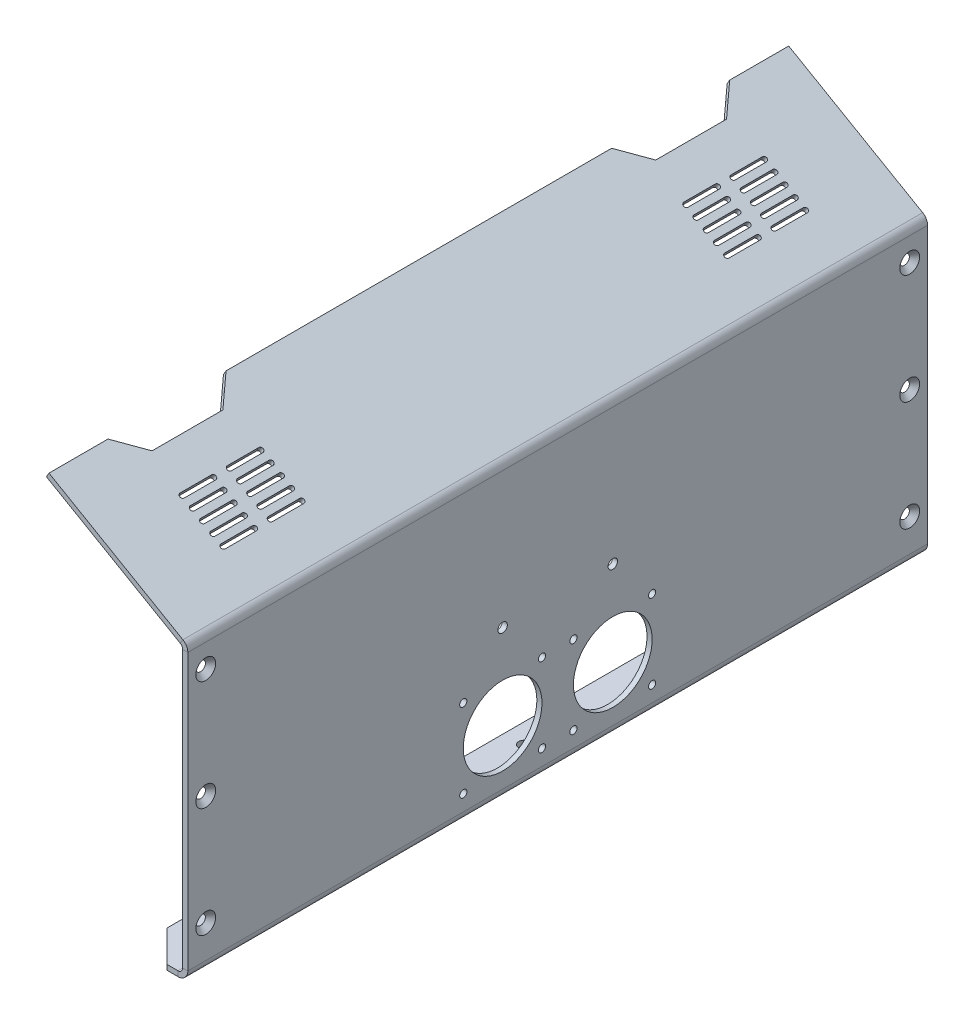
SolidWorks part; units mm, degrees
note: The reader was unsure of these and kept them because the rebuilt part matched: bend radius of "BaseBend1", "BaseBend2".
material "5052-H32"
ref_plane "Front Plane" through (0, 0, 0) normal (0, 0, 1) x (1, 0, 0)
ref_plane "Top Plane" through (0, 0, 0) normal (0, 1, 0) x (1, 0, 0)
ref_plane "Right Plane" through (0, 0, 0) normal (1, 0, 0) x (0, 0, -1)
sketch "Sketch1" plane through (0, 0, 0) normal (0, 0, 1) x (1, 0, 0)
  line L0 (-30, 0) -> (0, 0)
  line L1 (0, 0) -> (0, 180)
  line L2 (0, 180) -> (-86.6025, 230)
  dimension "D1" = 30
  dimension "D2" = 180
  dimension "D3" = 120
  dimension "D4" = 100
base flange "Base-Flange1" sketch "Sketch1" end condition mid plane depth 470 reverse direction no thickness 3.26 reverse thickness direction no bend radius 3
bend "BaseBend1" bend radius 3 bend angle 90 parameters "D5"=1
bend "BaseBend2" bend radius 3 bend angle 60 parameters "D5"=3
sketch "Sketch6" plane through (0, 0, 0) normal (0, 1, 0) x (1, 0, 0)
  line L1 (-17.387, -0.5952) -> (-17.387, -200.5952) construction
  line L2 (-17.387, -0.5952) -> (-17.387, 199.4048) construction
  circle A0 centre (-17.387, -0.5952) radius 3.5
  circle A1 centre (-17.387, -200.5952) radius 3.5
  circle A2 centre (-17.387, -100.5952) radius 3.5
  circle A3 centre (-17.387, 199.4048) radius 3.5
  circle A4 centre (-17.387, 99.4048) radius 3.5
  dimension "D2" = 7
  dimension "D1" = 200
extrude "Cut-Extrude1" cut sketch "Sketch6" against normal blind 10 normal cut yes
sketch "Sketch7" plane through (0, 0, 0) normal (0, 1, 0) x (1, 0, 0)
  line L0 (0, 0) -> (-64.8841, 0) construction
  line L1 (-30, -115.5952) -> (-3, -142.5952)
  line L2 (-30, -235) -> (-30, 235) construction
  line L3 (-3, -142.5952) -> (-3, -158.5952)
  line L4 (-3, -158.5952) -> (-30, -185.5952)
  line L5 (-3, -235) -> (-3, 235) construction
  line L6 (-30, -115.5952) -> (-30, -185.5952)
  line L7 (-30, 115.5952) -> (-30, 185.5952)
  line L8 (-3, 158.5952) -> (-30, 185.5952)
  line L9 (-3, 142.5952) -> (-3, 158.5952)
  line L10 (-30, 115.5952) -> (-3, 142.5952)
  circle A0 centre (-17.387, -100.5952) radius 3.5 construction
  circle A1 centre (-17.387, -200.5952) radius 3.5 construction
  dimension "D1" = 15
  dimension "D2" = 15
extrude "Cut-Extrude2" [suppressed] cut sketch "Sketch7" against normal up to surface (3.175 mm away)
chamfer "Chamfer1" distance 20 angle 45 2 edges at (-30, -1.63, 235) (-30, -1.63, -235)
sketch "Sketch8" plane through (3.26, 0, 0) normal (1, 0, 0) x (0, 0, -1)
  line L0 (0, 0) -> (0, 178.2679) construction
  line L1 (-235, 178.2679) -> (235, 178.2679) construction
  circle A0 centre (-223.6192, 163.426) radius 3
  circle A1 centre (-223.6192, 93.576) radius 3
  circle A2 centre (-223.6192, 23.726) radius 3
  circle A3 centre (223.6192, 23.726) radius 3
  circle A4 centre (223.6192, 93.576) radius 3
  circle A5 centre (223.6192, 163.426) radius 3
  dimension "D1" = 6
extrude "Cut-Extrude3" cut sketch "Sketch8" against normal up to surface (3.26 mm away) normal cut yes up to face at (0, 90.634, 0)
sketch "Sketch9" [suppressed] plane through (0, -3.175, 0) normal (0, -1, 0) x (-1, 0, 0)
  line L0 (3.048, -163.048) -> (25, -185) construction
  line L1 (14.024, -174.024) -> (-3.175, -174.024)
  line L2 (14.024, -174.024) -> (14.024, -125.976)
  line L3 (14.024, -125.976) -> (-3.175, -125.976)
  line L4 (-3.175, -174.024) -> (-3.175, -125.976)
  line L5 (25, -115) -> (3.048, -136.952) construction
  line L6 (-3.175, -235) -> (-3.175, 235) construction
  line L7 (0, 0) -> (25, 0) construction
  line L8 (25, -115) -> (25, 115) construction
  line L9 (-3.175, 174.024) -> (-3.175, 125.976)
  line L10 (14.024, 125.976) -> (-3.175, 125.976)
  line L11 (14.024, 174.024) -> (14.024, 125.976)
  line L12 (14.024, 174.024) -> (-3.175, 174.024)
extrude "Cut-Extrude4" [suppressed] cut sketch "Sketch9" against normal blind 15
sketch "Sketch10" plane through (79.5723, 137.8232, 0) normal (0.5, 0.866, 0) x (0.866, -0.5, 0)
  line L1 (-163.366, 177.5) -> (-118.366, 177.5)
  line L2 (-163.366, 177.5) -> (-163.366, 92.5)
  line L3 (-163.366, 92.5) -> (-118.366, 92.5)
  line L4 (-118.366, 177.5) -> (-118.366, 92.5)
  line L5 (-163.366, 177.5) -> (-118.366, 92.5) construction
  line L6 (-163.366, 92.5) -> (-118.366, 177.5) construction
  line L7 (-91.7321, 235) -> (-190, 235) construction
  point P0 (-140.866, 135)
  point P10 (-140.866, 235)
  dimension "D1" = 45
  dimension "D2" = 85
  dimension "D3" = 100
sketch "Sketch11" plane through (3.26, 0, 0) normal (1, 0, 0) x (0, 0, -1)
  line L0 (0, 3) -> (0, 178.2679) construction
  line L1 (-235, 3) -> (235, 3) construction
  line L2 (-235, 178.2679) -> (235, 178.2679) construction
  line L3 (-10, 63) -> (-60, 63) construction
  line L4 (-10, 63) -> (-10, 13) construction
  line L5 (-10, 13) -> (-60, 13) construction
  line L6 (-60, 63) -> (-60, 13) construction
  line L7 (-10, 63) -> (-60, 13) construction
  line L8 (-10, 13) -> (-60, 63) construction
  line L9 (10, 13) -> (60, 63) construction
  line L10 (10, 63) -> (60, 13) construction
  line L11 (60, 63) -> (60, 13) construction
  line L12 (10, 13) -> (60, 13) construction
  line L13 (10, 63) -> (10, 13) construction
  line L14 (10, 63) -> (60, 63) construction
  circle A0 centre (-60, 63) radius 2.286
  circle A1 centre (-10, 63) radius 2.286
  circle A2 centre (-10, 13) radius 2.286
  circle A3 centre (-60, 13) radius 2.286
  circle A4 centre (-35, 38) radius 25
  circle A5 centre (35, 38) radius 25
  circle A6 centre (60, 13) radius 2.286
  circle A7 centre (10, 13) radius 2.286
  circle A8 centre (10, 63) radius 2.286
  circle A9 centre (60, 63) radius 2.286
  point P6 (-35, 38)
  dimension "D3" = 4.572
  dimension "D1" = 35
  dimension "D2" = 35
  dimension "D4" = 50
extrude "Cut-Extrude5" cut sketch "Sketch11" against normal up to surface (3.26 mm away) normal cut yes up to face at (0, 163.426, -220.6192)
sketch "Sketch12" plane through (79.5723, 137.8232, 0) normal (0.5, 0.866, 0) x (0.866, -0.5, 0)
  line L0 (-91.7321, -235) -> (-190, -235) construction
  line L2 (-190, -235) -> (-190, 235) construction
  circle A0 centre (-130, -155) radius 10
  circle A1 centre (-130, -115) radius 10
  dimension "D1" = 20
  dimension "D2" = 80
  dimension "D3" = 40
  dimension "D4" = 60
sketch "Sketch14" plane through (0, 0, 0) normal (-1, 0, 0) x (0, 0, 1)
  circle A0 centre (35, 91.949) radius 3
  circle A1 centre (-35, 91.949) radius 3
  dimension "D1" = 6
extrude "Cut-Extrude7" cut sketch "Sketch14" against normal blind 10 normal cut yes
sketch "Sketch15" plane through (79.5723, 137.8232, 0) normal (0.5, 0.866, 0) x (0.866, -0.5, 0)
  line L0 (-150, -165) -> (-150, -185) construction
  line L1 (-148.5, -165) -> (-148.5, -185)
  line L2 (-151.5, -165) -> (-151.5, -185)
  line L3 (-91.7321, -235) -> (-190, -235) construction
  line L4 (-190, -235) -> (-190, 235) construction
  line L5 (-142.5, -165) -> (-142.5, -185) construction
  line L6 (-141, -165) -> (-141, -185)
  line L7 (-144, -165) -> (-144, -185)
  line L8 (-135, -165) -> (-135, -185) construction
  line L9 (-133.5, -165) -> (-133.5, -185)
  line L10 (-136.5, -165) -> (-136.5, -185)
  line L11 (-127.5, -165) -> (-127.5, -185) construction
  line L12 (-126, -165) -> (-126, -185)
  line L13 (-129, -165) -> (-129, -185)
  line L14 (-120, -165) -> (-120, -185) construction
  line L15 (-118.5, -165) -> (-118.5, -185)
  line L16 (-121.5, -165) -> (-121.5, -185)
  line L17 (-142.5, -135) -> (-142.5, -155) construction
  line L18 (-141, -135) -> (-141, -155)
  line L19 (-144, -135) -> (-144, -155)
  line L20 (-135, -135) -> (-135, -155) construction
  line L21 (-133.5, -135) -> (-133.5, -155)
  line L22 (-136.5, -135) -> (-136.5, -155)
  line L23 (-127.5, -135) -> (-127.5, -155) construction
  line L24 (-126, -135) -> (-126, -155)
  line L25 (-129, -135) -> (-129, -155)
  line L26 (-120, -135) -> (-120, -155) construction
  line L27 (-118.5, -135) -> (-118.5, -155)
  line L28 (-121.5, -135) -> (-121.5, -155)
  line L29 (-150, -135) -> (-150, -155) construction
  line L30 (-148.5, -135) -> (-148.5, -155)
  line L31 (-151.5, -135) -> (-151.5, -155)
  line L32 (-150, -165) -> (-142.5, -165) construction
  line L33 (-150, -165) -> (-150, -135) construction
  line L34 (-190, 0) -> (-91.7321, 0) construction
  line L35 (-91.7321, -235) -> (-91.7321, 235) construction
  line L36 (-150, 165) -> (-150, 185) construction
  line L37 (-148.5, 165) -> (-148.5, 185)
  line L38 (-151.5, 165) -> (-151.5, 185)
  line L39 (-142.5, 165) -> (-142.5, 185) construction
  line L40 (-141, 165) -> (-141, 185)
  line L41 (-144, 165) -> (-144, 185)
  line L42 (-135, 165) -> (-135, 185) construction
  line L43 (-133.5, 165) -> (-133.5, 185)
  line L44 (-136.5, 165) -> (-136.5, 185)
  line L45 (-127.5, 165) -> (-127.5, 185) construction
  line L46 (-126, 165) -> (-126, 185)
  line L47 (-129, 165) -> (-129, 185)
  line L48 (-120, 165) -> (-120, 185) construction
  line L49 (-118.5, 165) -> (-118.5, 185)
  line L50 (-121.5, 165) -> (-121.5, 185)
  line L51 (-142.5, 135) -> (-142.5, 155) construction
  line L52 (-141, 135) -> (-141, 155)
  line L53 (-144, 135) -> (-144, 155)
  line L54 (-135, 135) -> (-135, 155) construction
  line L55 (-133.5, 135) -> (-133.5, 155)
  line L56 (-136.5, 135) -> (-136.5, 155)
  line L57 (-127.5, 135) -> (-127.5, 155) construction
  line L58 (-126, 135) -> (-126, 155)
  line L59 (-129, 135) -> (-129, 155)
  line L60 (-120, 135) -> (-120, 155) construction
  line L61 (-118.5, 135) -> (-118.5, 155)
  line L62 (-121.5, 135) -> (-121.5, 155)
  line L63 (-150, 135) -> (-150, 155) construction
  line L64 (-148.5, 135) -> (-148.5, 155)
  line L65 (-151.5, 135) -> (-151.5, 155)
  line L66 (-150, 165) -> (-150, 135) construction
  line L67 (-150, 165) -> (-142.5, 165) construction
  arc A0 (-148.5, -165) -> (-151.5, -165) centre (-150, -165) ccw
  arc A1 (-151.5, -185) -> (-148.5, -185) centre (-150, -185) ccw
  arc A2 (-141, -165) -> (-144, -165) centre (-142.5, -165) ccw
  arc A3 (-144, -185) -> (-141, -185) centre (-142.5, -185) ccw
  arc A4 (-133.5, -165) -> (-136.5, -165) centre (-135, -165) ccw
  arc A5 (-136.5, -185) -> (-133.5, -185) centre (-135, -185) ccw
  arc A6 (-126, -165) -> (-129, -165) centre (-127.5, -165) ccw
  arc A7 (-129, -185) -> (-126, -185) centre (-127.5, -185) ccw
  arc A8 (-118.5, -165) -> (-121.5, -165) centre (-120, -165) ccw
  arc A9 (-121.5, -185) -> (-118.5, -185) centre (-120, -185) ccw
  arc A10 (-141, -135) -> (-144, -135) centre (-142.5, -135) ccw
  arc A11 (-144, -155) -> (-141, -155) centre (-142.5, -155) ccw
  arc A12 (-133.5, -135) -> (-136.5, -135) centre (-135, -135) ccw
  arc A13 (-136.5, -155) -> (-133.5, -155) centre (-135, -155) ccw
  arc A14 (-126, -135) -> (-129, -135) centre (-127.5, -135) ccw
  arc A15 (-129, -155) -> (-126, -155) centre (-127.5, -155) ccw
  arc A16 (-118.5, -135) -> (-121.5, -135) centre (-120, -135) ccw
  arc A17 (-121.5, -155) -> (-118.5, -155) centre (-120, -155) ccw
  arc A18 (-148.5, -135) -> (-151.5, -135) centre (-150, -135) ccw
  arc A19 (-151.5, -155) -> (-148.5, -155) centre (-150, -155) ccw
  arc A20 (-148.5, 165) -> (-151.5, 165) centre (-150, 165) cw
  arc A21 (-151.5, 185) -> (-148.5, 185) centre (-150, 185) cw
  arc A22 (-141, 165) -> (-144, 165) centre (-142.5, 165) cw
  arc A23 (-144, 185) -> (-141, 185) centre (-142.5, 185) cw
  arc A24 (-133.5, 165) -> (-136.5, 165) centre (-135, 165) cw
  arc A25 (-136.5, 185) -> (-133.5, 185) centre (-135, 185) cw
  arc A26 (-126, 165) -> (-129, 165) centre (-127.5, 165) cw
  arc A27 (-129, 185) -> (-126, 185) centre (-127.5, 185) cw
  arc A28 (-118.5, 165) -> (-121.5, 165) centre (-120, 165) cw
  arc A29 (-121.5, 185) -> (-118.5, 185) centre (-120, 185) cw
  arc A30 (-141, 135) -> (-144, 135) centre (-142.5, 135) cw
  arc A31 (-144, 155) -> (-141, 155) centre (-142.5, 155) cw
  arc A32 (-133.5, 135) -> (-136.5, 135) centre (-135, 135) cw
  arc A33 (-136.5, 155) -> (-133.5, 155) centre (-135, 155) cw
  arc A34 (-126, 135) -> (-129, 135) centre (-127.5, 135) cw
  arc A35 (-129, 155) -> (-126, 155) centre (-127.5, 155) cw
  arc A36 (-118.5, 135) -> (-121.5, 135) centre (-120, 135) cw
  arc A37 (-121.5, 155) -> (-118.5, 155) centre (-120, 155) cw
  arc A38 (-148.5, 135) -> (-151.5, 135) centre (-150, 135) cw
  arc A39 (-151.5, 155) -> (-148.5, 155) centre (-150, 155) cw
  point P2 (-150, -175)
  point P15 (-142.5, -175)
  point P22 (-135, -175)
  point P29 (-127.5, -175)
  point P36 (-120, -175)
  point P43 (-142.5, -145)
  point P50 (-135, -145)
  point P57 (-127.5, -145)
  point P64 (-120, -145)
  point P71 (-150, -145)
  point P83 (-150, 175)
  point P90 (-142.5, 175)
  point P97 (-135, 175)
  point P104 (-127.5, 175)
  point P111 (-120, 175)
  point P118 (-142.5, 145)
  point P125 (-135, 145)
  point P132 (-127.5, 145)
  point P139 (-120, 145)
  point P146 (-150, 145)
  dimension "D2" = 1.5
  dimension "D1" = 60
  dimension "D3" = 40
  dimension "D4" = 20
  dimension "D7" = 7.5
  dimension "D8" = 30
  dimension "D5" = 5
  dimension "D6" = 2
extrude "Cut-Extrude8" cut sketch "Sketch15" against normal blind 10
sketch "Sketch16" plane through (79.5723, 137.8232, 0) normal (0.5, 0.866, 0) x (0.866, -0.5, 0)
  line L0 (-190, -235) -> (-190, 235) construction
  line L1 (-175, -130) -> (-190, -130)
  line L2 (-175, -130) -> (-175, -190)
  line L3 (-175, -190) -> (-190, -190)
  line L4 (-190, -130) -> (-190, -190)
  line L5 (-175, -130) -> (-190, -190) construction
  line L6 (-175, -190) -> (-190, -130) construction
  line L8 (-142.5, -156.5) -> (-142.5, -163.5) construction
  line L9 (-91.7321, 0) -> (-190, 0) construction
  line L10 (-91.7321, -235) -> (-91.7321, 235) construction
  line L11 (-142.5, 156.5) -> (-142.5, 163.5) construction
  line L12 (-175, 190) -> (-190, 130) construction
  line L13 (-175, 130) -> (-190, 190) construction
  line L14 (-190, 130) -> (-190, 190)
  line L15 (-175, 190) -> (-190, 190)
  line L16 (-175, 130) -> (-175, 190)
  line L17 (-175, 130) -> (-190, 130)
  arc A0 (-144, -155) -> (-141, -155) centre (-142.5, -155) ccw construction
  arc A1 (-141, -165) -> (-144, -165) centre (-142.5, -165) ccw construction
  point P0 (-182.5, -160)
  point P16 (-142.5, -160)
  point P27 (-142.5, 160)
  point P28 (-182.5, 160)
  dimension "D1" = 15
  dimension "D2" = 60
extrude "Cut-Extrude9" cut sketch "Sketch16" against normal blind 10 normal cut yes
chamfer "Chamfer2" distance 7.5 angle 45 8 edges at (-85.7875, 231.4116, -190) (-72.7972, 223.9116, -190) (-72.7972, 223.9116, -130) (-85.7875, 231.4116, -130) (-85.7875, 231.4116, 130) (-72.7972, 223.9116, 130) (-72.7972, 223.9116, 190) (-85.7875, 231.4116, 190)
chamfer "Chamfer3" distance 3.3 angle 45 6 edges at (3.26, 163.426, 220.6192) (3.26, 163.426, -220.6192) (3.26, 93.576, -220.6192) (3.26, 23.726, -220.6192) (3.26, 23.726, 220.6192) (3.26, 93.576, 220.6192)
sketch "Bend-Lines1" [suppressed] plane through (0, 0, 0) normal (0, 1, 0) x (1, 0, 0)
sketch "Bounding-Box1" [suppressed] plane through (0, 0, 0) normal (0, 1, 0) x (1, 0, 0)
sheet metal parameters "Sheet-Metal1" thickness 3.26 parameters "D1"=2.54
flat pattern "Flat-Pattern1" [suppressed]
sketch "Bend-Lines2" plane through (0, 0, 0) normal (-1, 0, 0) x (0, 0, 1)
  line L0 (235, -0.2) -> (-235, -0.2) construction
  line L1 (235, -0.2) -> (-235, -0.2) construction
sketch3d "Bounding-Box2" [suppressed]
  line L0 (-470, -25.4, 0) -> (0, -25.4, 0) construction
  line L1 (-470, 120, 0) -> (0, 120, 0) construction
  line L2 (-470, -25.4, 0) -> (-470, 120, 0) construction
  line L3 (0, -25.4, 0) -> (0, 120, 0) construction
bend of the flat pattern "Flatten-<BaseBend1>1"
bend of the flat pattern "Flatten-<BaseBend2>1"
sheet metal parameters "Sheet-Metal2" thickness 3.26 parameters "D1"=2.54
flat pattern "Flat-Pattern1" [suppressed]
sketch "Bend-Lines2" plane through (0, 0, 0) normal (-1, 0, 0) x (0, 0, 1)
  line L0 (235, -0.2) -> (-235, -0.2) construction
  line L1 (235, -0.2) -> (-235, -0.2) construction
sketch3d "Bounding-Box2" [suppressed]
  line L0 (-470, -25.4, 0) -> (0, -25.4, 0) construction
  line L1 (-470, 120, 0) -> (0, 120, 0) construction
  line L2 (-470, -25.4, 0) -> (-470, 120, 0) construction
  line L3 (0, -25.4, 0) -> (0, 120, 0) construction
bend of the flat pattern "Flatten-<BaseBend1>1"
bend of the flat pattern "Flatten-<BaseBend2>2"
sheet metal parameters "Sheet-Metal3" thickness 3.26 parameters "D1"=2.54
flat pattern "Flat-Pattern1" [suppressed]
sketch "Bend-Lines2" plane through (0, 0, 0) normal (-1, 0, 0) x (0, 0, 1)
  line L0 (235, -0.2) -> (-235, -0.2) construction
  line L1 (235, -0.2) -> (-235, -0.2) construction
sketch3d "Bounding-Box2" [suppressed]
  line L0 (-470, -25.4, 0) -> (0, -25.4, 0) construction
  line L1 (-470, 120, 0) -> (0, 120, 0) construction
  line L2 (-470, -25.4, 0) -> (-470, 120, 0) construction
  line L3 (0, -25.4, 0) -> (0, 120, 0) construction
bend of the flat pattern "Flatten-<BaseBend1>1"
bend of the flat pattern "Flatten-<BaseBend2>3"
sheet metal parameters "Sheet-Metal4" thickness 3.26 parameters "D1"=2.54
flat pattern "Flat-Pattern1"
sketch "Bend-Lines2" plane through (0, 0, 0) normal (-1, 0, 0) x (0, 0, 1)
  line L0 (235, -0.8176) -> (-235, -0.8176) construction
  line L1 (235, -0.8176) -> (-235, -0.8176) construction
  line L2 (-235, 181.7737) -> (235, 181.7737) construction
  line L3 (-235, 181.7737) -> (235, 181.7737) construction
sketch3d "Bounding-Box2" [suppressed]
  line L0 (-470, -26.6352, 0) -> (0, -26.6352, 0) construction
  line L1 (-470, 282.4974, 0) -> (0, 282.4974, 0) construction
  line L2 (-470, -26.6352, 0) -> (-470, 282.4974, 0) construction
  line L3 (0, -26.6352, 0) -> (0, 282.4974, 0) construction
bend of the flat pattern "Flatten-<BaseBend1>1"
bend of the flat pattern "Flatten-<BaseBend2>4"
sheet metal parameters "Sheet-Metal6" thickness 3.26 parameters "D1"=2.54
flat pattern "Flat-Pattern1"
sketch "Bend-Lines2" plane through (0, 0, 0) normal (-1, 0, 0) x (0, 0, 1)
  line L0 (235, -0.8176) -> (-235, -0.8176) construction
  line L1 (235, -0.8176) -> (-235, -0.8176) construction
  line L2 (-235, 181.7737) -> (235, 181.7737) construction
  line L3 (-235, 181.7737) -> (235, 181.7737) construction
sketch3d "Bounding-Box2" [suppressed]
  line L0 (-470, -26.6352, 0) -> (0, -26.6352, 0) construction
  line L1 (-470, 282.4974, 0) -> (0, 282.4974, 0) construction
  line L2 (-470, -26.6352, 0) -> (-470, 282.4974, 0) construction
  line L3 (0, -26.6352, 0) -> (0, 282.4974, 0) construction
bend of the flat pattern "Flatten-<BaseBend1>1"
bend of the flat pattern "Flatten-<BaseBend2>4"
sheet metal parameters "Sheet-Metal8" thickness 3.26 parameters "D1"=2.54
flat pattern "Flat-Pattern1" [suppressed]
sketch "Bend-Lines2" plane through (0, 0, 0) normal (-1, 0, 0) x (0, 0, 1)
  line L0 (235, -0.5927) -> (-235, -0.5927) construction
  line L1 (235, -0.5927) -> (-235, -0.5927) construction
  line L2 (-235, 180.6674) -> (235, 180.6674) construction
  line L3 (-235, 180.6674) -> (235, 180.6674) construction
sketch3d "Bounding-Box2" [suppressed]
  line L0 (-470, -31.1854, 0) -> (0, -31.1854, 0) construction
  line L1 (-470, 281.3348, 0) -> (0, 281.3348, 0) construction
  line L2 (-470, -31.1854, 0) -> (-470, 281.3348, 0) construction
  line L3 (0, -31.1854, 0) -> (0, 281.3348, 0) construction
bend of the flat pattern "Flatten-<BaseBend1>1"
bend of the flat pattern "Flatten-<BaseBend2>4"
sketch "Sketch12-1" plane through (3.175, 91.3348, 0) normal (1, 0, 0) x (0, -1, 0)
  line L0 (102.5202, -235) -> (-190, -235) construction
  line L2 (-190, -235) -> (-190, 235) construction
  circle A0 centre (-130, -155) radius 10
  circle A1 centre (-130, -115) radius 10
  dimension "D1" = 20
  dimension "D2" = 80
  dimension "D3" = 40
  dimension "D4" = 60
sheet metal parameters "Sheet-Metal21" thickness 3.26 parameters "D1"=2.54
flat pattern "Flat-Pattern1" [suppressed]
sketch "Bend-Lines2" plane through (0, 0, 0) normal (-1, 0, 0) x (0, 0, 1)
  line L0 (235, -0.5927) -> (-235, -0.5927) construction
  line L1 (235, -0.5927) -> (-235, -0.5927) construction
  line L2 (-235, 180.6674) -> (235, 180.6674) construction
  line L3 (-235, 180.6674) -> (235, 180.6674) construction
sketch3d "Bounding-Box2" [suppressed]
  line L0 (-470, -31.1854, 0) -> (0, -31.1854, 0) construction
  line L1 (-470, 281.3348, 0) -> (0, 281.3348, 0) construction
  line L2 (-470, -31.1854, 0) -> (-470, 281.3348, 0) construction
  line L3 (0, -31.1854, 0) -> (0, 281.3348, 0) construction
bend of the flat pattern "Flatten-<BaseBend1>1"
bend of the flat pattern "Flatten-<BaseBend2>4"
sketch "Sketch12-1" plane through (3.175, 91.3348, 0) normal (1, 0, 0) x (0, -1, 0)
  line L0 (102.5202, -235) -> (-190, -235)
  line L2 (-190, -235) -> (-190, 235)
  circle A0 centre (-130, -155) radius 10
  circle A1 centre (-130, -115) radius 10
  dimension "D1" = 20
  dimension "D2" = 80
  dimension "D3" = 40
  dimension "D4" = 60
sheet metal parameters "Sheet-Metal22" thickness 3.26 parameters "D1"=2.54
flat pattern "Flat-Pattern1" [suppressed]
sketch "Bend-Lines2" plane through (0, 0, 0) normal (-1, 0, 0) x (0, 0, 1)
  line L0 (235, -0.5927) -> (-235, -0.5927) construction
  line L1 (235, -0.5927) -> (-235, -0.5927) construction
  line L2 (-235, 180.6674) -> (235, 180.6674) construction
  line L3 (-235, 180.6674) -> (235, 180.6674) construction
sketch3d "Bounding-Box2" [suppressed]
  line L0 (-470, -31.1854, 0) -> (0, -31.1854, 0) construction
  line L1 (-470, 281.3348, 0) -> (0, 281.3348, 0) construction
  line L2 (-470, -31.1854, 0) -> (-470, 281.3348, 0) construction
  line L3 (0, -31.1854, 0) -> (0, 281.3348, 0) construction
bend of the flat pattern "Flatten-<BaseBend1>1"
bend of the flat pattern "Flatten-<BaseBend2>4"
sketch "Sketch12-1" plane through (3.175, 91.3348, 0) normal (1, 0, 0) x (0, -1, 0)
  line L0 (102.5202, -235) -> (-190, -235)
  line L2 (-190, -235) -> (-190, 235)
  circle A0 centre (-130, -155) radius 10
  circle A1 centre (-130, -115) radius 10
  dimension "D1" = 20
  dimension "D2" = 80
  dimension "D3" = 40
  dimension "D4" = 60
sheet metal parameters "Sheet-Metal23" thickness 3.26 parameters "D1"=2.54
flat pattern "Flat-Pattern1" [suppressed]
sketch "Bend-Lines2" plane through (0, 0, 0) normal (-1, 0, 0) x (0, 0, 1)
  line L0 (235, -0.5927) -> (-235, -0.5927) construction
  line L1 (235, -0.5927) -> (-235, -0.5927) construction
  line L2 (-235, 180.6674) -> (235, 180.6674) construction
  line L3 (-235, 180.6674) -> (235, 180.6674) construction
sketch3d "Bounding-Box2" [suppressed]
  line L0 (-470, -31.1854, 0) -> (0, -31.1854, 0) construction
  line L1 (-470, 281.3348, 0) -> (0, 281.3348, 0) construction
  line L2 (-470, -31.1854, 0) -> (-470, 281.3348, 0) construction
  line L3 (0, -31.1854, 0) -> (0, 281.3348, 0) construction
bend of the flat pattern "Flatten-<BaseBend1>1"
bend of the flat pattern "Flatten-<BaseBend2>4"
sketch "Sketch12-1" plane through (3.175, 91.3348, 0) normal (1, 0, 0) x (0, -1, 0)
  line L0 (102.5202, -235) -> (-190, -235)
  line L2 (-190, -235) -> (-190, 235)
  circle A0 centre (-130, -155) radius 10
  circle A1 centre (-130, -115) radius 10
  dimension "D1" = 20
  dimension "D2" = 80
  dimension "D3" = 40
  dimension "D4" = 60
